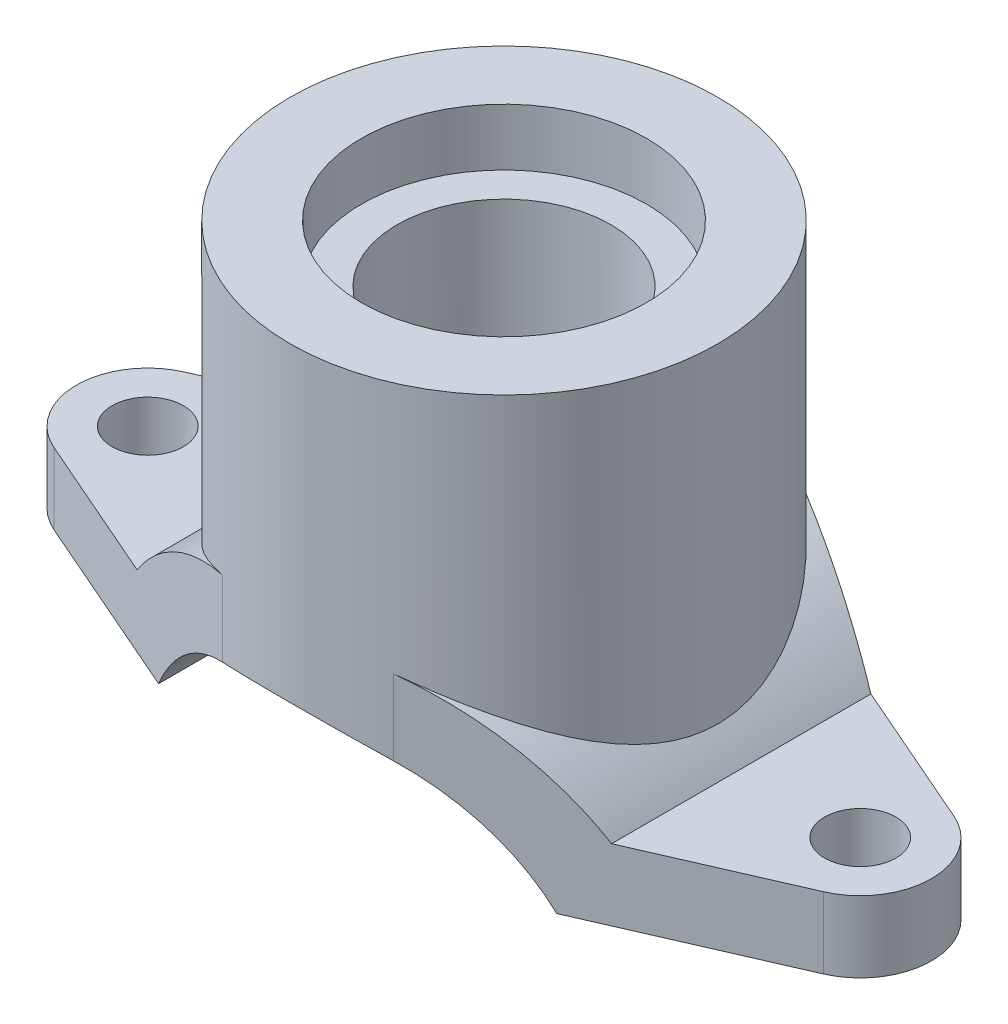
SolidWorks part; units mm, degrees
ref_plane "Front Plane" through (0, 0, 0) normal (0, 0, 1) x (1, 0, 0)
ref_plane "Top Plane" through (0, 0, 0) normal (0, 1, 0) x (1, 0, 0)
ref_plane "Right Plane" through (0, 0, 0) normal (1, 0, 0) x (0, 0, -1)
sketch "Sketch1" plane through (0, 0, 0) normal (0, 0, 1) x (1, 0, 0)
  line L0 (-150, 0) -> (-69.8498, 0)
  line L1 (150, 0) -> (150, 25)
  line L2 (150, 25) -> (83.2406, 25)
  line L3 (-150, 0) -> (-150, 25)
  line L4 (-150, 25) -> (-83.2406, 25)
  line L5 (69.8498, 0) -> (150, 0)
  arc A0 (-69.8498, 0) -> (69.8498, 0) centre (0, -39) cw
  arc A1 (-83.2406, 25) -> (83.2406, 25) centre (0, -39) cw
  point P3 (0, 0)
  point P4 (0, 0)
  point P6 (0, 0)
  point P13 (0, 0)
  point P14 (0, 0)
  point P15 (-16.4812, 25)
  point P16 (-16.4812, 25)
  dimension "D3" = 39
  dimension "D4" = 80
  dimension "D5" = 105
  dimension "D1" = 300
  dimension "D2" = 25
  dimension "D6" = 150
extrude "Boss-Extrude1" add sketch "Sketch1" along normal mid plane 150
sketch "Sketch2" plane through (0, 0, 0) normal (0, 1, 0) x (1, 0, 0)
  line L0 (0, 0) -> (0, -50000) construction
  line L4 (-30, 68.7386) -> (-135, 22.9129)
  line L5 (-30, -68.7386) -> (-135, -22.9129)
  line L6 (30, -68.7386) -> (135, -22.9129)
  line L7 (30, 68.7386) -> (135, 22.9129)
  circle A0 centre (0, 0) radius 75
  circle A1 centre (0, 0) radius 37.5
  circle A2 centre (0, 0) radius 50
  circle A3 centre (125, 0) radius 25
  circle A4 centre (125, 0) radius 12.5
  circle A5 centre (-125, 0) radius 12.5
  circle A6 centre (-125, 0) radius 25
  dimension "D1" = 150
  dimension "D2" = 75
  dimension "D3" = 100
  dimension "D4" = 50
  dimension "D5" = 25
  dimension "D6" = 250
extrude "Cut-Extrude1" cut sketch "Sketch2" along normal through all flip side to cut contours A6 A5 | L4 A6 L5 A0 | L0 A0 A2 | L0 A2 A1 | A1 L0 | A2 L0 A1 | A0 L0 A2 | L0 A1 | A3 L7 A0 L6 | A3 A4 | A4 | A5 region at (-34.3553, 0, -34.3553) region at (-14.8898, 0, 71.3414) region at (-25.7665, 0, -25.7665) region at (-85.9478, 0, 0) region at (85.9478, 0, 0) region at (-149.2929, 0, 0) region at (100.7071, 0, 0) region at (125, 0, 0) region at (-125, 0, 0)
extrude "Cut-Extrude2" cut sketch "Sketch2<3>" along normal through all contours A5 | A4 region at (125, 0, 0) region at (-125, 0, 0)
sketch "Sketch2<3>" plane through (0, 0, 0) normal (0, 1, 0) x (1, 0, 0) same geometry as "Sketch2"
ref_plane "Plane1" through (0, 150, 0) normal (0, 1, 0) x (1, 0, 0)
sketch "Sketch3" plane through (0, 150, 0) normal (0, 1, 0) x (1, 0, 0)
  circle A0 centre (0, 0) radius 75
  circle A1 centre (0, 0) radius 37.5
  circle A2 centre (0, 0) radius 50
  dimension "D1" = 150
  dimension "D2" = 75
  dimension "D3" = 100
extrude "Boss-Extrude2" add sketch "Sketch3" against normal up to surface (84 mm away) contours A0 A2 | A2 A1 | A1 region at (-72.8787, 150, 0) region at (0, 150, 0) region at (-48.5858, 150, 0) up to face at (0, 46.3911, 0)
sketch "Sketch4" plane through (0, 0, 0) normal (0, 0, 1) x (1, 0, 0)
  line L0 (0, 0) -> (0, 50000) construction
  line L1 (0, 150) -> (50, 150)
  line L2 (75, 150) -> (-75, 150) construction
  line L3 (50, 150) -> (50, 130)
  line L4 (50, 130) -> (37.5, 130)
  line L5 (37.5, 130) -> (37.5, 25.3133)
  line L6 (37.5, 25.3133) -> (0, 25.3133)
  line L7 (0, 25.3133) -> (0, 150)
  dimension "D1" = 20
  dimension "D2" = 100
  dimension "D3" = 75
revolve "Cut-Revolve1" cut sketch "Sketch4" angle 360 about L0
